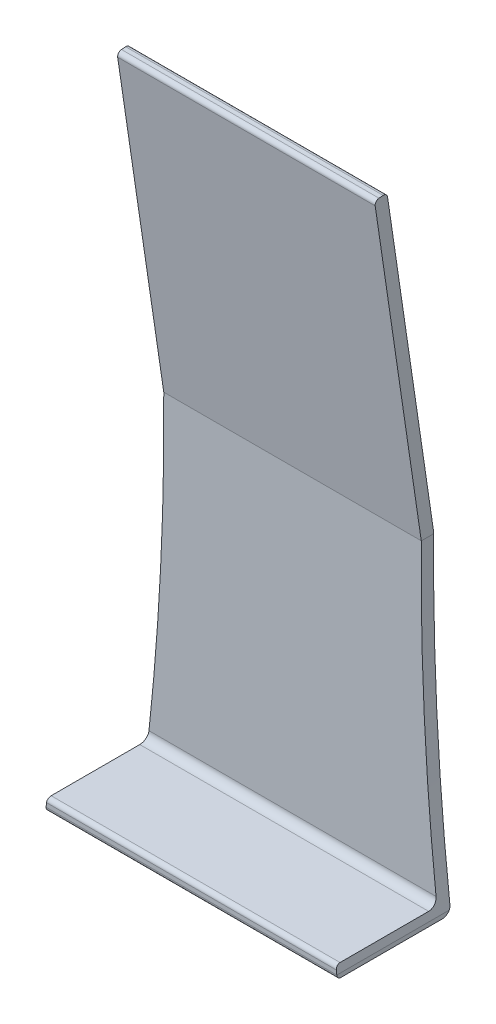
SolidWorks part; units mm, degrees
ref_plane "Front Plane" through (0, 0, 0) normal (0, 0, 1) x (1, 0, 0)
ref_plane "Top Plane" through (0, 0, 0) normal (0, 1, 0) x (1, 0, 0)
ref_plane "Right Plane" through (0, 0, 0) normal (1, 0, 0) x (0, 0, -1)
sketch "Sketch1" plane through (0, 0, 0) normal (1, 0, 0) x (0, 0, -1)
  line L0 (1, 0) -> (25.3342, 0)
  line L1 (0, 1) -> (0, 2)
  line L2 (1, 3) -> (22.3342, 3)
  line L3 (27.3342, 2) -> (27.3342, 77.5771)
  line L4 (24.3342, 5) -> (24.3342, 77.3575)
  line L5 (27.3342, 77.5771) -> (16.2174, 153.1149)
  line L6 (24.3342, 77.3575) -> (13.2388, 152.7505)
  line L7 (14.1551, 153.8935) -> (15.1551, 153.9666)
  arc A0 (1, 0) -> (0, 1) centre (1, 1) cw
  arc A1 (0, 2) -> (1, 3) centre (1, 2) cw
  arc A2 (13.2388, 152.7505) -> (14.1551, 153.8935) centre (14.2281, 152.8961) cw
  arc A3 (16.2174, 153.1149) -> (15.1551, 153.9666) centre (15.2281, 152.9693) ccw
  arc A4 (25.3342, 0) -> (27.3342, 2) centre (25.3342, 2) ccw
  arc A5 (22.3342, 3) -> (24.3342, 5) centre (22.3342, 5) ccw
  point P11 (0, 0)
  point P16 (13.0821, 153.8149)
  point P19 (16.0821, 154.0345)
  dimension "D5" = 1
  dimension "D6" = 2
  dimension "D8" = 72.3575
  dimension "D1" = 3
  dimension "D2" = 3
  dimension "D3" = 3
  dimension "D4" = 3
  dimension "D7" = 75.5771
  dimension "D9" = 24.3342
extrude "Boss-Extrude1" add sketch "Sketch1" along normal blind 70
sketch "Sketch2" plane through (0, 0, 0) normal (0, 0, 1) x (1, 0, 0)
  line L5 (0, 1) -> (0, 154.25)
  line L6 (70, 154.25) -> (66, 154.25)
  line L7 (0, 154.25) -> (4, 154.25)
  line L8 (4, 154.25) -> (4, 77.3575)
  line L12 (70, 77.3575) -> (0, 77.3575) construction
  line L15 (70, 1) -> (70, 154.25)
  line L16 (66, 154.25) -> (66, 77.3575)
  spline S0 degree 2 poles (4, 77.3575) (4.3611, 39.1058) (0, 1) knots 0 0 0 1 1 1
  spline S1 degree 2 poles (66, 77.3575) (65.6389, 39.1058) (70, 1) knots 0 0 0 1 1 1
  dimension "D1" = 4
extrude "Cut-Extrude4" cut sketch "Sketch2" against normal blind 70
sketch "Sketch4" plane through (0, 5.582, -37.9296) normal (0, 0.1456, -0.9893) x (-1, 0, 0)
  line L0 (-4, 141.622) -> (-66, 141.622) construction
  line L1 (-4, 72.7706) -> (-4, 149.122) construction
  line L2 (-66, 149.122) -> (-66, 72.7706) construction
  line L3 (-8.5, 149.122) -> (-8.5, 72.7706) construction
  line L4 (-66, 149.122) -> (-4, 149.122) construction
  line L5 (-66, 72.7706) -> (-4, 72.7706) construction
  line L6 (-66, 149.122) -> (-66, 72.5533) construction
  line L7 (-66, 72.5533) -> (-4, 72.7706) construction
  line L8 (-4, 72.7706) -> (-4, 149.122) construction
  line L9 (-4, 149.122) -> (-66, 149.122) construction
  line L10 (-61.5, 149.122) -> (-61.5, 72.5691) construction
  dimension "D1" = 4.5
  dimension "D2" = 4.5
  dimension "D3" = 7.5
